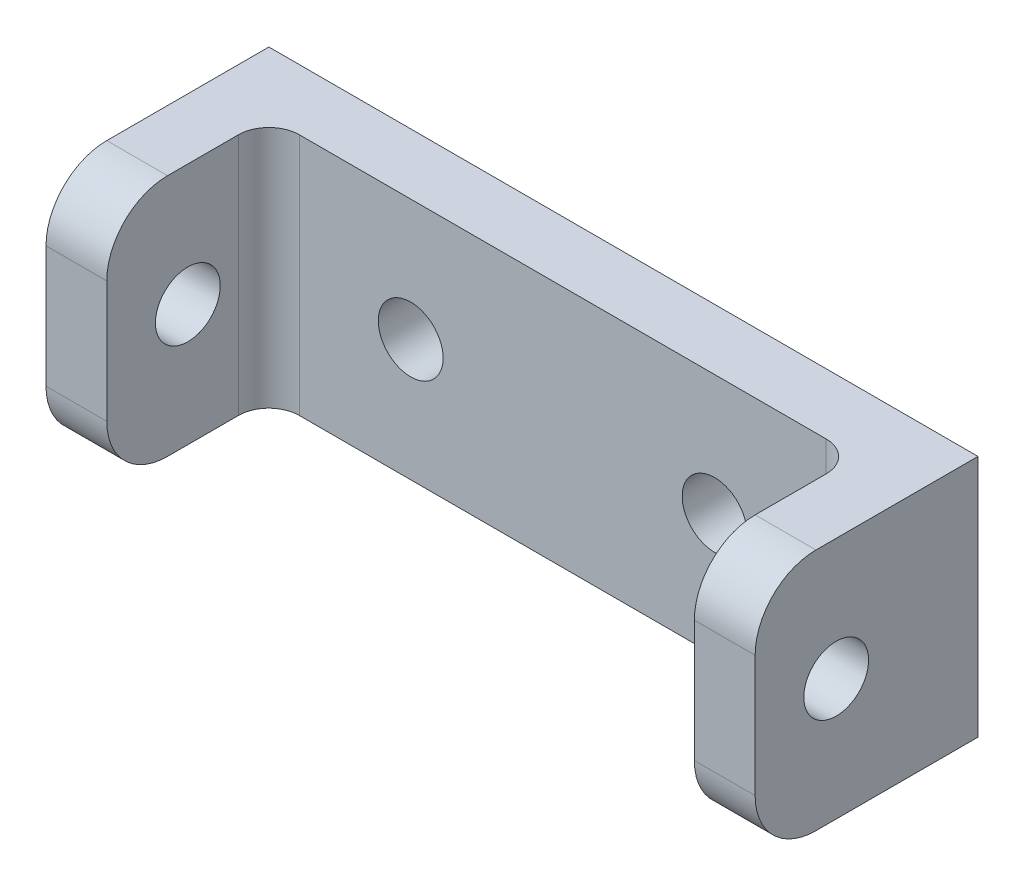
SolidWorks part; units mm, degrees
material "6061-O (SS)"
ref_plane "前视基准面" through (0, 0, 0) normal (0, 0, 1) x (1, 0, 0)
ref_plane "上视基准面" through (0, 0, 0) normal (0, 1, 0) x (1, 0, 0)
ref_plane "右视基准面" through (0, 0, 0) normal (1, 0, 0) x (0, 0, -1)
sketch "草图1" plane through (0, 0, 0) normal (0, 0, 1) x (1, 0, 0)
  line L0 (40, -26.5152) -> (40, 26.5152) construction
  line L1 (17.5, -30) -> (-17.5, -30)
  line L2 (17.5, -30) -> (17.5, -18)
  line L3 (17.5, -18) -> (-17.5, -18)
  line L4 (-17.5, -30) -> (-17.5, -18)
  line L5 (-26.5, -40) -> (-24.7426, -40) construction
  dimension "D1" = 12
  dimension "D2" = 35
  dimension "D3" = 22.5
  dimension "D4" = 10
extrude "凸台-拉伸1" add sketch "草图1" along normal blind 3
sketch "草图2" plane through (-17.5, 0, 0) normal (-1, 0, 0) x (0, 0, 1)
  line L1 (3, -30) -> (11, -30)
  line L2 (3, -30) -> (3, -18)
  line L3 (3, -18) -> (11, -18)
  line L4 (11, -30) -> (11, -18)
  dimension "D1" = 12
  dimension "D2" = 8
extrude "凸台-拉伸2" add sketch "草图2" against normal blind 3
fillet "圆角1" radius 3 2 edges at (-16, -18, 11) (-16, -30, 11)
fillet "圆角2" radius 1.5 1 edges at (-14.5, -24, 3)
sketch "草图3" plane through (-17.5, 0, 0) normal (-1, 0, 0) x (0, 0, 1)
  line L0 (11, -27) -> (11, -21) construction
  line L1 (8, -30) -> (0, -30) construction
  circle A0 centre (7, -24) radius 1.6
  dimension "D1" = 3.2
  dimension "D2" = 4
  dimension "D3" = 6
extrude "切除-拉伸1" cut sketch "草图3" against normal blind 3
sketch "草图4" plane through (0, 0, 3) normal (0, 0, 1) x (1, 0, 0)
  line L0 (-13, -30) -> (17.5, -30) construction
  line L1 (17.5, -30) -> (17.5, -18) construction
  circle A0 centre (7.5, -24) radius 1.6
  circle A1 centre (-7.5, -24) radius 1.6
  dimension "D1" = 3.2
  dimension "D2" = 6
  dimension "D3" = 6
  dimension "D4" = 15
  dimension "D5" = 10
extrude "切除-拉伸2" cut sketch "草图4" against normal blind 3
mirror "镜向1" about plane through (0, 0, 0) normal (1, 0, 0) of "切除-拉伸1", "圆角2", "圆角1", "凸台-拉伸2"
